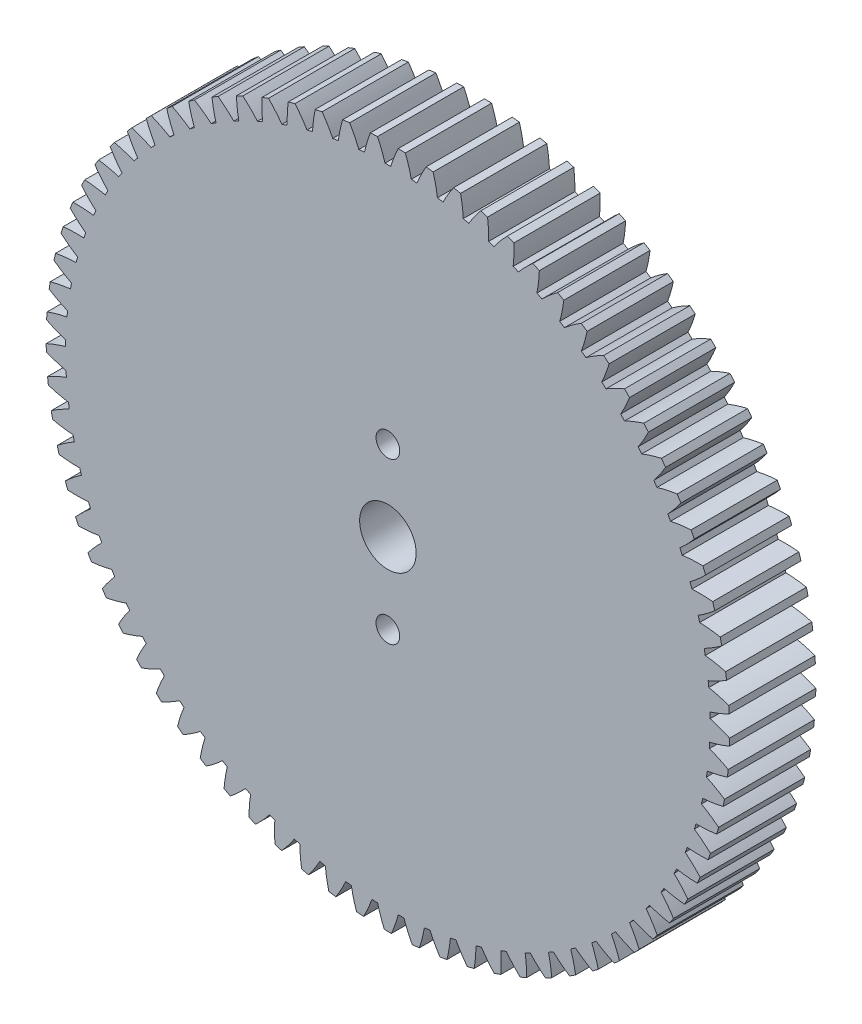
SolidWorks part; units mm, degrees
ref_plane "Front Plane" through (0, 0, 0) normal (0, 0, 1) x (1, 0, 0)
ref_plane "Top Plane" through (0, 0, 0) normal (0, 1, 0) x (1, 0, 0)
ref_plane "Right Plane" through (0, 0, 0) normal (1, 0, 0) x (0, 0, -1)
sketch "Model" plane through (0, 0, 0) normal (0, 0, 1) x (1, 0, 0)
  circle A3 centre (0, -9.3) radius 1.375
  circle A4 centre (0, 0) radius 3.275
  circle A5 centre (0, 9.3) radius 1.375
  arc A311 (-39.5739, 2.0126) -> (-37.3581, 1.0914) centre (-32.524, 15.8446) ccw
  arc A312 (-37.3581, 1.0914) -> (-37.3715, 0.4333) centre (0, 0) ccw
  arc A313 (-37.3715, 0.4333) -> (-39.623, -0.3968) centre (-33.1432, -14.5048) ccw
  arc A314 (-39.623, -0.3968) -> (-39.6062, -1.2197) centre (0, 0) ccw
  arc A315 (-39.6062, -1.2197) -> (-37.3227, -1.9572) centre (-33.7072, 13.1409) ccw
  arc A316 (-37.3227, -1.9572) -> (-37.2825, -2.6143) centre (0, 0) ccw
  arc A317 (-37.2825, -2.6143) -> (-39.4588, -3.6251) centre (-31.8506, -17.158) ccw
  arc A318 (-39.4588, -3.6251) -> (-39.375, -4.4439) centre (0, 0) ccw
  arc A319 (-39.375, -4.4439) -> (-37.039, -4.9929) centre (-34.6662, 10.3497) ccw
  arc A320 (-37.039, -4.9929) -> (-36.9453, -5.6445) centre (0, 0) ccw
  arc A321 (-36.9453, -5.6445) -> (-39.0321, -6.8293) centre (-30.3461, -19.6971) ccw
  arc A322 (-39.0321, -6.8293) -> (-38.8818, -7.6386) centre (0, 0) ccw
  arc A323 (-38.8818, -7.6386) -> (-36.5088, -7.9953) centre (-35.3944, 7.4897) ccw
  arc A324 (-36.5088, -7.9953) -> (-36.3623, -8.6371) centre (0, 0) ccw
  arc A325 (-36.3623, -8.6371) -> (-38.3455, -9.988) centre (-28.6396, -22.105) ccw
  arc A326 (-38.3455, -9.988) -> (-38.1298, -10.7824) centre (0, 0) ccw
  arc A327 (-38.1298, -10.7824) -> (-35.7356, -10.9445) centre (-35.8871, 4.5798) ccw
  arc A328 (-35.7356, -10.9445) -> (-35.5373, -11.5722) centre (0, 0) ccw
  arc A329 (-35.5373, -11.5722) -> (-37.4038, -13.0803) centre (-26.7426, -24.3659) ccw
  arc A330 (-37.4038, -13.0803) -> (-37.124, -13.8544) centre (0, 0) ccw
  arc A331 (-37.124, -13.8544) -> (-34.7246, -13.8209) centre (-36.141, 1.6394) ccw
  arc A332 (-34.7246, -13.8209) -> (-34.4758, -14.4303) centre (0, 0) ccw
  arc A333 (-34.4758, -14.4303) -> (-36.2132, -16.0856) centre (-24.6675, -26.4646) ccw
  arc A334 (-36.2132, -16.0856) -> (-35.8713, -16.8343) centre (0, 0) ccw
  arc A335 (-35.8713, -16.8343) -> (-33.4826, -16.6052) centre (-36.1544, -1.3119) ccw
  arc A336 (-33.4826, -16.6052) -> (-33.1849, -17.1924) centre (0, 0) ccw
  arc A337 (-33.1849, -17.1924) -> (-34.7816, -18.9838) centre (-22.4283, -28.3871) ccw
  arc A338 (-34.7816, -18.9838) -> (-34.3797, -19.7021) centre (0, 0) ccw
  arc A339 (-34.3797, -19.7021) -> (-32.0177, -19.2791) centre (-35.9271, -4.2544) ccw
  arc A340 (-32.0177, -19.2791) -> (-31.6731, -19.8401) centre (0, 0) ccw
  arc A341 (-31.6731, -19.8401) -> (-33.1185, -21.7556) centre (-20.0399, -30.1208) ccw
  arc A342 (-33.1185, -21.7556) -> (-32.6594, -22.4388) centre (0, 0) ccw
  arc A343 (-32.6594, -22.4388) -> (-30.3397, -21.8247) centre (-35.4608, -7.1687) ccw
  arc A344 (-30.3397, -21.8247) -> (-29.9506, -22.3557) centre (0, 0) ccw
  arc A345 (-29.9506, -22.3557) -> (-31.235, -24.3827) centre (-17.5181, -31.654) ccw
  arc A346 (-31.235, -24.3827) -> (-30.7218, -25.0262) centre (0, 0) ccw
  arc A347 (-30.7218, -25.0262) -> (-28.4598, -24.2251) centre (-34.7585, -10.0352) ccw
  arc A348 (-28.4598, -24.2251) -> (-28.0287, -24.7226) centre (0, 0) ccw
  arc A349 (-28.0287, -24.7226) -> (-29.1437, -26.8475) centre (-14.8797, -32.9766) ccw
  arc A350 (-29.1437, -26.8475) -> (-28.5797, -27.4471) centre (0, 0) ccw
  arc A351 (-28.5797, -27.4471) -> (-26.3906, -26.4642) centre (-33.8249, -12.835) ccw
  arc A352 (-26.3906, -26.4642) -> (-25.9204, -26.9249) centre (0, 0) ccw
  arc A353 (-25.9204, -26.9249) -> (-26.8584, -29.1336) centre (-12.1423, -34.0797) ccw
  arc A354 (-26.8584, -29.1336) -> (-26.2474, -29.6852) centre (0, 0) ccw
  arc A355 (-26.2474, -29.6852) -> (-24.1457, -28.5272) centre (-32.6662, -15.5493) ccw
  arc A356 (-24.1457, -28.5272) -> (-23.6395, -28.9481) centre (0, 0) ccw
  arc A357 (-23.6395, -28.9481) -> (-24.3943, -31.2259) centre (-9.3241, -34.956) ccw
  arc A358 (-24.3943, -31.2259) -> (-23.7405, -31.7259) centre (0, 0) ccw
  arc A359 (-23.7405, -31.7259) -> (-21.7401, -30.4004) centre (-31.2901, -18.1602) ccw
  arc A360 (-21.7401, -30.4004) -> (-21.2013, -30.7786) centre (0, 0) ccw
  arc A361 (-21.2013, -30.7786) -> (-21.768, -33.1104) centre (-6.4438, -35.5997) ccw
  arc A362 (-21.768, -33.1104) -> (-21.0755, -33.5554) centre (0, 0) ccw
  arc A363 (-21.0755, -33.5554) -> (-19.1898, -32.0713) centre (-29.7057, -20.6502) ccw
  arc A364 (-19.1898, -32.0713) -> (-18.622, -32.4043) centre (0, 0) ccw
  arc A365 (-18.622, -32.4043) -> (-18.9967, -34.7745) centre (-3.5207, -36.0065) ccw
  arc A366 (-18.9967, -34.7745) -> (-18.2703, -35.1616) centre (0, 0) ccw
  arc A367 (-18.2703, -35.1616) -> (-16.5119, -33.5287) centre (-27.9237, -23.0027) ccw
  arc A368 (-16.5119, -33.5287) -> (-15.9188, -33.8143) centre (0, 0) ccw
  arc A369 (-15.9188, -33.8143) -> (-16.0991, -36.2072) centre (-0.5741, -36.1736) ccw
  arc A370 (-16.0991, -36.2072) -> (-15.3435, -36.5338) centre (0, 0) ccw
  arc A371 (-15.3435, -36.5338) -> (-13.724, -34.763) centre (-25.9559, -25.2022) ccw
  arc A372 (-13.724, -34.763) -> (-13.1096, -34.9993) centre (0, 0) ccw
  arc A373 (-13.1096, -34.9993) -> (-13.0943, -37.3989) centre (2.3763, -36.1) ccw
  arc A374 (-13.0943, -37.3989) -> (-12.3146, -37.6629) centre (0, 0) ccw
  arc A375 (-12.3146, -37.6629) -> (-10.8449, -35.766) centre (-23.8153, -27.234) ccw
  arc A376 (-10.8449, -35.766) -> (-10.2133, -35.9514) centre (0, 0) ccw
  arc A377 (-10.2133, -35.9514) -> (-10.0024, -38.3418) centre (5.3109, -35.7862) ccw
  arc A378 (-10.0024, -38.3418) -> (-9.2038, -38.5413) centre (0, 0) ccw
  arc A379 (-9.2038, -38.5413) -> (-7.8935, -36.5309) centre (-21.5162, -29.0846) ccw
  arc A380 (-7.8935, -36.5309) -> (-7.2489, -36.6643) centre (0, 0) ccw
  arc A381 (-7.2489, -36.6643) -> (-6.8439, -39.0295) centre (8.2101, -35.2343) ccw
  arc A382 (-6.8439, -39.0295) -> (-6.0317, -39.1632) centre (0, 0) ccw
  arc A383 (-6.0317, -39.1632) -> (-4.8897, -37.0528) centre (-19.074, -30.7416) ccw
  arc A384 (-4.8897, -37.0528) -> (-4.2363, -37.1331) centre (0, 0) ccw
  arc A385 (-4.2363, -37.1331) -> (-3.6398, -39.4575) centre (11.0547, -34.4478) ccw
  arc A386 (-3.6398, -39.4575) -> (-2.8194, -39.5246) centre (0, 0) ccw
  arc A387 (-2.8194, -39.5246) -> (-1.8532, -37.328) centre (-16.5048, -32.194) ccw
  arc A388 (-1.8532, -37.328) -> (-1.1955, -37.3549) centre (0, 0) ccw
  arc A389 (-1.1955, -37.3549) -> (-0.4116, -39.6229) centre (13.8257, -33.4321) ccw
  arc A390 (-0.4116, -39.6229) -> (0.4116, -39.6229) centre (0, 0) ccw
  arc A391 (0.4116, -39.6229) -> (1.1955, -37.3549) centre (-13.8257, -33.4321) ccw
  arc A392 (1.1955, -37.3549) -> (1.8532, -37.328) centre (0, 0) ccw
  arc A393 (1.8532, -37.328) -> (2.8194, -39.5246) centre (16.5048, -32.194) ccw
  arc A394 (2.8194, -39.5246) -> (3.6398, -39.4575) centre (0, 0) ccw
  arc A395 (3.6398, -39.4575) -> (4.2363, -37.1331) centre (-11.0547, -34.4478) ccw
  arc A396 (4.2363, -37.1331) -> (4.8897, -37.0528) centre (0, 0) ccw
  arc A397 (4.8897, -37.0528) -> (6.0317, -39.1632) centre (19.074, -30.7416) ccw
  arc A398 (6.0317, -39.1632) -> (6.8439, -39.0295) centre (0, 0) ccw
  arc A399 (6.8439, -39.0295) -> (7.2489, -36.6643) centre (-8.2101, -35.2343) ccw
  arc A400 (7.2489, -36.6643) -> (7.8935, -36.5309) centre (0, 0) ccw
  arc A401 (7.8935, -36.5309) -> (9.2038, -38.5413) centre (21.5162, -29.0846) ccw
  arc A402 (9.2038, -38.5413) -> (10.0024, -38.3418) centre (0, 0) ccw
  arc A403 (10.0024, -38.3418) -> (10.2133, -35.9514) centre (-5.3109, -35.7862) ccw
  arc A404 (10.2133, -35.9514) -> (10.8449, -35.766) centre (0, 0) ccw
  arc A405 (10.8449, -35.766) -> (12.3146, -37.6629) centre (23.8153, -27.234) ccw
  arc A406 (12.3146, -37.6629) -> (13.0943, -37.3989) centre (0, 0) ccw
  arc A407 (13.0943, -37.3989) -> (13.1096, -34.9993) centre (-2.3763, -36.1) ccw
  arc A408 (13.1096, -34.9993) -> (13.724, -34.763) centre (0, 0) ccw
  arc A409 (13.724, -34.763) -> (15.3435, -36.5338) centre (25.9559, -25.2022) ccw
  arc A410 (15.3435, -36.5338) -> (16.0991, -36.2072) centre (0, 0) ccw
  arc A411 (16.0991, -36.2072) -> (15.9188, -33.8143) centre (0.5741, -36.1736) ccw
  arc A412 (15.9188, -33.8143) -> (16.5119, -33.5287) centre (0, 0) ccw
  arc A413 (16.5119, -33.5287) -> (18.2703, -35.1616) centre (27.9237, -23.0027) ccw
  arc A414 (18.2703, -35.1616) -> (18.9967, -34.7745) centre (0, 0) ccw
  arc A415 (18.9967, -34.7745) -> (18.622, -32.4043) centre (3.5207, -36.0065) ccw
  arc A416 (18.622, -32.4043) -> (19.1898, -32.0713) centre (0, 0) ccw
  arc A417 (19.1898, -32.0713) -> (21.0755, -33.5554) centre (29.7057, -20.6502) ccw
  arc A418 (21.0755, -33.5554) -> (21.768, -33.1104) centre (0, 0) ccw
  arc A419 (21.768, -33.1104) -> (21.2013, -30.7786) centre (6.4438, -35.5997) ccw
  arc A420 (21.2013, -30.7786) -> (21.7401, -30.4004) centre (0, 0) ccw
  arc A421 (21.7401, -30.4004) -> (23.7405, -31.7259) centre (31.2901, -18.1602) ccw
  arc A422 (23.7405, -31.7259) -> (24.3943, -31.2259) centre (0, 0) ccw
  arc A423 (24.3943, -31.2259) -> (23.6395, -28.9481) centre (9.3241, -34.956) ccw
  arc A424 (23.6395, -28.9481) -> (24.1457, -28.5272) centre (0, 0) ccw
  arc A425 (24.1457, -28.5272) -> (26.2474, -29.6852) centre (32.6662, -15.5493) ccw
  arc A426 (26.2474, -29.6852) -> (26.8584, -29.1336) centre (0, 0) ccw
  arc A427 (26.8584, -29.1336) -> (25.9204, -26.9249) centre (12.1423, -34.0797) ccw
  arc A428 (25.9204, -26.9249) -> (26.3906, -26.4642) centre (0, 0) ccw
  arc A429 (26.3906, -26.4642) -> (28.5797, -27.4471) centre (33.8249, -12.835) ccw
  arc A430 (28.5797, -27.4471) -> (29.1437, -26.8475) centre (0, 0) ccw
  arc A431 (29.1437, -26.8475) -> (28.0287, -24.7226) centre (14.8797, -32.9766) ccw
  arc A432 (28.0287, -24.7226) -> (28.4598, -24.2251) centre (0, 0) ccw
  arc A433 (28.4598, -24.2251) -> (30.7218, -25.0262) centre (34.7585, -10.0352) ccw
  arc A434 (30.7218, -25.0262) -> (31.235, -24.3827) centre (0, 0) ccw
  arc A435 (31.235, -24.3827) -> (29.9506, -22.3557) centre (17.5181, -31.654) ccw
  arc A436 (29.9506, -22.3557) -> (30.3397, -21.8247) centre (0, 0) ccw
  arc A437 (30.3397, -21.8247) -> (32.6594, -22.4388) centre (35.4608, -7.1687) ccw
  arc A438 (32.6594, -22.4388) -> (33.1185, -21.7556) centre (0, 0) ccw
  arc A439 (33.1185, -21.7556) -> (31.6731, -19.8401) centre (20.0399, -30.1208) ccw
  arc A440 (31.6731, -19.8401) -> (32.0177, -19.2791) centre (0, 0) ccw
  arc A441 (32.0177, -19.2791) -> (34.3797, -19.7021) centre (35.9271, -4.2544) ccw
  arc A442 (34.3797, -19.7021) -> (34.7816, -18.9838) centre (0, 0) ccw
  arc A443 (34.7816, -18.9838) -> (33.1849, -17.1924) centre (22.4283, -28.3871) ccw
  arc A444 (33.1849, -17.1924) -> (33.4826, -16.6052) centre (0, 0) ccw
  arc A445 (33.4826, -16.6052) -> (35.8713, -16.8343) centre (36.1544, -1.3119) ccw
  arc A446 (35.8713, -16.8343) -> (36.2132, -16.0856) centre (0, 0) ccw
  arc A447 (36.2132, -16.0856) -> (34.4758, -14.4303) centre (24.6675, -26.4646) ccw
  arc A448 (34.4758, -14.4303) -> (34.7246, -13.8209) centre (0, 0) ccw
  arc A449 (34.7246, -13.8209) -> (37.124, -13.8544) centre (36.141, 1.6394) ccw
  arc A450 (37.124, -13.8544) -> (37.4038, -13.0803) centre (0, 0) ccw
  arc A451 (37.4038, -13.0803) -> (35.5373, -11.5722) centre (26.7426, -24.3659) ccw
  arc A452 (35.5373, -11.5722) -> (35.7356, -10.9445) centre (0, 0) ccw
  arc A453 (35.7356, -10.9445) -> (38.1298, -10.7824) centre (35.8871, 4.5798) ccw
  arc A454 (38.1298, -10.7824) -> (38.3455, -9.988) centre (0, 0) ccw
  arc A455 (38.3455, -9.988) -> (36.3623, -8.6371) centre (28.6396, -22.105) ccw
  arc A456 (36.3623, -8.6371) -> (36.5088, -7.9953) centre (0, 0) ccw
  arc A457 (36.5088, -7.9953) -> (38.8818, -7.6386) centre (35.3944, 7.4897) ccw
  arc A458 (38.8818, -7.6386) -> (39.0321, -6.8293) centre (0, 0) ccw
  arc A459 (39.0321, -6.8293) -> (36.9453, -5.6445) centre (30.3461, -19.6971) ccw
  arc A460 (36.9453, -5.6445) -> (37.039, -4.9929) centre (0, 0) ccw
  arc A461 (37.039, -4.9929) -> (39.375, -4.4439) centre (34.6662, 10.3497) ccw
  arc A462 (39.375, -4.4439) -> (39.4588, -3.6251) centre (0, 0) ccw
  arc A463 (39.4588, -3.6251) -> (37.2825, -2.6143) centre (31.8506, -17.158) ccw
  arc A464 (37.2825, -2.6143) -> (37.3227, -1.9572) centre (0, 0) ccw
  arc A465 (37.3227, -1.9572) -> (39.6062, -1.2197) centre (33.7072, 13.1409) ccw
  arc A466 (39.6062, -1.2197) -> (39.623, -0.3968) centre (0, 0) ccw
  arc A467 (39.623, -0.3968) -> (37.3715, 0.4333) centre (33.1432, -14.5048) ccw
  arc A468 (37.3715, 0.4333) -> (37.3581, 1.0914) centre (0, 0) ccw
  arc A469 (37.3581, 1.0914) -> (39.5739, 2.0126) centre (32.524, 15.8446) ccw
  arc A470 (39.5739, 2.0126) -> (39.5235, 2.8342) centre (0, 0) ccw
  arc A471 (39.5235, 2.8342) -> (37.2118, 3.478) centre (34.2152, -11.7551) ccw
  arc A472 (37.2118, 3.478) -> (37.1448, 4.1328) centre (0, 0) ccw
  arc A473 (37.1448, 4.1328) -> (39.2781, 5.2315) centre (31.1243, 18.4429) ccw
  arc A474 (39.2781, 5.2315) -> (39.161, 6.0463) centre (0, 0) ccw
  arc A475 (39.161, 6.0463) -> (36.8045, 6.4995) centre (35.0595, -8.9271) ccw
  arc A476 (36.8045, 6.4995) -> (36.6843, 7.1467) centre (0, 0) ccw
  arc A477 (36.6843, 7.1467) -> (38.721, 8.4157) centre (29.5174, 20.9185) ccw
  arc A478 (38.721, 8.4157) -> (38.5379, 9.2182) centre (0, 0) ccw
  arc A479 (38.5379, 9.2182) -> (36.1523, 9.4778) centre (35.6705, -6.0397) ccw
  arc A480 (36.1523, 9.4778) -> (35.9797, 10.113) centre (0, 0) ccw
  arc A481 (35.9797, 10.113) -> (37.9062, 11.5438) centre (27.7142, 23.2548) ccw
  arc A482 (37.9062, 11.5438) -> (37.6583, 12.3287) centre (0, 0) ccw
  arc A483 (37.6583, 12.3287) -> (35.2595, 12.393) centre (36.0441, -3.1122) ccw
  arc A484 (35.2595, 12.393) -> (35.0357, 13.0121) centre (0, 0) ccw
  arc A485 (35.0357, 13.0121) -> (36.8392, 14.5951) centre (25.7265, 25.4364) ccw
  arc A486 (36.8392, 14.5951) -> (36.5281, 15.3572) centre (0, 0) ccw
  arc A487 (36.5281, 15.3572) -> (34.132, 15.2257) centre (36.1778, -0.1639) ccw
  arc A488 (34.132, 15.2257) -> (33.8585, 15.8245) centre (0, 0) ccw
  arc A489 (33.8585, 15.8245) -> (35.5269, 17.5493) centre (23.5676, 27.4487) ccw
  arc A490 (35.5269, 17.5493) -> (35.1548, 18.2834) centre (0, 0) ccw
  arc A491 (35.1548, 18.2834) -> (32.7774, 17.9571) centre (36.0708, 2.7855) ccw
  arc A492 (32.7774, 17.9571) -> (32.456, 18.5316) centre (0, 0) ccw
  arc A493 (32.456, 18.5316) -> (33.9783, 20.3866) centre (21.2518, 29.2783) ccw
  arc A494 (33.9783, 20.3866) -> (33.5475, 21.088) centre (0, 0) ccw
  arc A495 (33.5475, 21.088) -> (31.2047, 20.569) centre (35.7237, 5.7163) ccw
  arc A496 (31.2047, 20.569) -> (30.8375, 21.1154) centre (0, 0) ccw
  arc A497 (30.8375, 21.1154) -> (32.2035, 23.0884) centre (18.7946, 30.9131) ccw
  arc A498 (32.2035, 23.0884) -> (31.717, 23.7523) centre (0, 0) ccw
  arc A499 (31.717, 23.7523) -> (29.4243, 23.0441) centre (35.1389, 8.6091) ccw
  arc A500 (29.4243, 23.0441) -> (29.0138, 23.5587) centre (0, 0) ccw
  arc A501 (29.0138, 23.5587) -> (30.2145, 25.6364) centre (16.2124, 32.3422) ccw
  arc A502 (30.2145, 25.6364) -> (29.6754, 26.2585) centre (0, 0) ccw
  arc A503 (29.6754, 26.2585) -> (27.448, 25.3657) centre (34.3203, 11.4446) ccw
  arc A504 (27.448, 25.3657) -> (26.997, 25.8452) centre (0, 0) ccw
  arc A505 (26.997, 25.8452) -> (28.0243, 28.0139) centre (13.5223, 33.556) ccw
  arc A506 (28.0243, 28.0139) -> (27.4364, 28.5899) centre (0, 0) ccw
  arc A507 (27.4364, 28.5899) -> (25.2892, 27.5186) centre (33.2732, 14.2039) ccw
  arc A508 (25.2892, 27.5186) -> (24.8006, 27.9598) centre (0, 0) ccw
  arc A509 (24.8006, 27.9598) -> (25.6477, 30.2049) centre (10.7421, 34.5466) ccw
  arc A510 (25.6477, 30.2049) -> (25.0148, 30.7311) centre (0, 0) ccw
  arc A511 (25.0148, 30.7311) -> (22.962, 29.4883) centre (32.0048, 16.8688) ccw
  arc A512 (22.962, 29.4883) -> (22.4391, 29.8882) centre (0, 0) ccw
  arc A513 (22.4391, 29.8882) -> (23.1004, 32.1949) centre (7.8905, 35.3072) ccw
  arc A514 (23.1004, 32.1949) -> (22.4266, 32.6678) centre (0, 0) ccw
  arc A515 (22.4266, 32.6678) -> (20.482, 31.2618) centre (30.5233, 19.4213) ccw
  arc A516 (20.482, 31.2618) -> (19.9282, 31.6177) centre (0, 0) ccw
  arc A517 (19.9282, 31.6177) -> (20.3993, 33.9707) centre (4.9864, 35.8329) ccw
  arc A518 (20.3993, 33.9707) -> (19.6893, 34.3871) centre (0, 0) ccw
  arc A519 (19.6893, 34.3871) -> (17.8657, 32.8273) centre (28.8387, 21.8446) ccw
  arc A520 (17.8657, 32.8273) -> (17.2848, 33.1369) centre (0, 0) ccw
  arc A521 (17.2848, 33.1369) -> (17.5625, 35.5204) centre (2.0491, 36.1201) ccw
  arc A522 (17.5625, 35.5204) -> (16.8209, 35.8775) centre (0, 0) ccw
  arc A523 (16.8209, 35.8775) -> (15.1306, 34.1743) centre (26.9622, 24.1226) ccw
  arc A524 (15.1306, 34.1743) -> (14.5263, 34.4355) centre (0, 0) ccw
  arc A525 (14.5263, 34.4355) -> (14.6088, 36.8337) centre (-0.9018, 36.1669) ccw
  arc A526 (14.6088, 36.8337) -> (13.8406, 37.1292) centre (0, 0) ccw
  arc A527 (13.8406, 37.1292) -> (12.2947, 35.2939) centre (24.9063, 26.24) ccw
  arc A528 (12.2947, 35.2939) -> (11.6712, 35.5049) centre (0, 0) ccw
  arc A529 (11.6712, 35.5049) -> (11.5579, 37.9019) centre (-3.8468, 35.9731) ccw
  arc A530 (11.5579, 37.9019) -> (10.7682, 38.1338) centre (0, 0) ccw
  arc A531 (10.7682, 38.1338) -> (9.377, 36.1786) centre (22.6846, 28.1828) ccw
  arc A532 (9.377, 36.1786) -> (8.7384, 36.3381) centre (0, 0) ccw
  arc A533 (8.7384, 36.3381) -> (8.4301, 38.7179) centre (-6.7661, 35.5398) ccw
  arc A534 (8.4301, 38.7179) -> (7.6241, 38.8846) centre (0, 0) ccw
  arc A535 (7.6241, 38.8846) -> (6.3969, 36.8225) centre (20.312, 29.938) ccw
  arc A536 (6.3969, 36.8225) -> (5.7474, 36.9294) centre (0, 0) ccw
  arc A537 (5.7474, 36.9294) -> (5.2462, 39.2762) centre (-9.6404, 34.8701) ccw
  arc A538 (5.2462, 39.2762) -> (4.4292, 39.3767) centre (0, 0) ccw
  arc A539 (4.4292, 39.3767) -> (3.3743, 37.2214) centre (17.8042, 31.494) ccw
  arc A540 (3.3743, 37.2214) -> (2.7182, 37.275) centre (0, 0) ccw
  arc A541 (2.7182, 37.275) -> (2.0274, 39.5731) centre (-12.4506, 33.9683) ccw
  arc A542 (2.0274, 39.5731) -> (1.2049, 39.6067) centre (0, 0) ccw
  arc A543 (1.2049, 39.6067) -> (0.3291, 37.3726) centre (15.1779, 32.8404) ccw
  arc A544 (0.3291, 37.3726) -> (-0.3291, 37.3726) centre (0, 0) ccw
  arc A545 (-0.3291, 37.3726) -> (-1.2049, 39.6067) centre (-15.1779, 32.8404) ccw
  arc A546 (-1.2049, 39.6067) -> (-2.0274, 39.5731) centre (0, 0) ccw
  arc A547 (-2.0274, 39.5731) -> (-2.7182, 37.275) centre (12.4506, 33.9683) ccw
  arc A548 (-2.7182, 37.275) -> (-3.3743, 37.2214) centre (0, 0) ccw
  arc A549 (-3.3743, 37.2214) -> (-4.4292, 39.3767) centre (-17.8042, 31.494) ccw
  arc A550 (-4.4292, 39.3767) -> (-5.2462, 39.2762) centre (0, 0) ccw
  arc A551 (-5.2462, 39.2762) -> (-5.7474, 36.9294) centre (9.6404, 34.8701) ccw
  arc A552 (-5.7474, 36.9294) -> (-6.3969, 36.8225) centre (0, 0) ccw
  arc A553 (-6.3969, 36.8225) -> (-7.6241, 38.8846) centre (-20.312, 29.938) ccw
  arc A554 (-7.6241, 38.8846) -> (-8.4301, 38.7179) centre (0, 0) ccw
  arc A555 (-8.4301, 38.7179) -> (-8.7384, 36.3381) centre (6.7661, 35.5398) ccw
  arc A556 (-8.7384, 36.3381) -> (-9.377, 36.1786) centre (0, 0) ccw
  arc A557 (-9.377, 36.1786) -> (-10.7682, 38.1338) centre (-22.6846, 28.1828) ccw
  arc A558 (-10.7682, 38.1338) -> (-11.5579, 37.9019) centre (0, 0) ccw
  arc A559 (-11.5579, 37.9019) -> (-11.6712, 35.5049) centre (3.8468, 35.9731) ccw
  arc A560 (-11.6712, 35.5049) -> (-12.2947, 35.2939) centre (0, 0) ccw
  arc A561 (-12.2947, 35.2939) -> (-13.8406, 37.1292) centre (-24.9063, 26.24) ccw
  arc A562 (-13.8406, 37.1292) -> (-14.6088, 36.8337) centre (0, 0) ccw
  arc A563 (-14.6088, 36.8337) -> (-14.5263, 34.4355) centre (0.9018, 36.1669) ccw
  arc A564 (-14.5263, 34.4355) -> (-15.1306, 34.1743) centre (0, 0) ccw
  arc A565 (-15.1306, 34.1743) -> (-16.8209, 35.8775) centre (-26.9622, 24.1226) ccw
  arc A566 (-16.8209, 35.8775) -> (-17.5625, 35.5204) centre (0, 0) ccw
  arc A567 (-17.5625, 35.5204) -> (-17.2848, 33.1369) centre (-2.0491, 36.1201) ccw
  arc A568 (-17.2848, 33.1369) -> (-17.8657, 32.8273) centre (0, 0) ccw
  arc A569 (-17.8657, 32.8273) -> (-19.6893, 34.3871) centre (-28.8387, 21.8446) ccw
  arc A570 (-19.6893, 34.3871) -> (-20.3993, 33.9707) centre (0, 0) ccw
  arc A571 (-20.3993, 33.9707) -> (-19.9282, 31.6177) centre (-4.9864, 35.8329) ccw
  arc A572 (-19.9282, 31.6177) -> (-20.482, 31.2618) centre (0, 0) ccw
  arc A573 (-20.482, 31.2618) -> (-22.4266, 32.6678) centre (-30.5233, 19.4213) ccw
  arc A574 (-22.4266, 32.6678) -> (-23.1004, 32.1949) centre (0, 0) ccw
  arc A575 (-23.1004, 32.1949) -> (-22.4391, 29.8882) centre (-7.8905, 35.3072) ccw
  arc A576 (-22.4391, 29.8882) -> (-22.962, 29.4883) centre (0, 0) ccw
  arc A577 (-22.962, 29.4883) -> (-25.0148, 30.7311) centre (-32.0048, 16.8688) ccw
  arc A578 (-25.0148, 30.7311) -> (-25.6477, 30.2049) centre (0, 0) ccw
  arc A579 (-25.6477, 30.2049) -> (-24.8006, 27.9598) centre (-10.7421, 34.5466) ccw
  arc A580 (-24.8006, 27.9598) -> (-25.2892, 27.5186) centre (0, 0) ccw
  arc A581 (-25.2892, 27.5186) -> (-27.4364, 28.5899) centre (-33.2732, 14.2039) ccw
  arc A582 (-27.4364, 28.5899) -> (-28.0243, 28.0139) centre (0, 0) ccw
  arc A583 (-28.0243, 28.0139) -> (-26.997, 25.8452) centre (-13.5223, 33.556) ccw
  arc A584 (-26.997, 25.8452) -> (-27.448, 25.3657) centre (0, 0) ccw
  arc A585 (-27.448, 25.3657) -> (-29.6754, 26.2585) centre (-34.3203, 11.4446) ccw
  arc A586 (-29.6754, 26.2585) -> (-30.2145, 25.6364) centre (0, 0) ccw
  arc A587 (-30.2145, 25.6364) -> (-29.0138, 23.5587) centre (-16.2124, 32.3422) ccw
  arc A588 (-29.0138, 23.5587) -> (-29.4243, 23.0441) centre (0, 0) ccw
  arc A589 (-29.4243, 23.0441) -> (-31.717, 23.7523) centre (-35.1389, 8.6091) ccw
  arc A590 (-31.717, 23.7523) -> (-32.2035, 23.0884) centre (0, 0) ccw
  arc A591 (-32.2035, 23.0884) -> (-30.8375, 21.1154) centre (-18.7946, 30.9131) ccw
  arc A592 (-30.8375, 21.1154) -> (-31.2047, 20.569) centre (0, 0) ccw
  arc A593 (-31.2047, 20.569) -> (-33.5475, 21.088) centre (-35.7237, 5.7163) ccw
  arc A594 (-33.5475, 21.088) -> (-33.9783, 20.3866) centre (0, 0) ccw
  arc A595 (-33.9783, 20.3866) -> (-32.456, 18.5316) centre (-21.2518, 29.2783) ccw
  arc A596 (-32.456, 18.5316) -> (-32.7774, 17.9571) centre (0, 0) ccw
  arc A597 (-32.7774, 17.9571) -> (-35.1548, 18.2834) centre (-36.0708, 2.7855) ccw
  arc A598 (-35.1548, 18.2834) -> (-35.5269, 17.5493) centre (0, 0) ccw
  arc A599 (-35.5269, 17.5493) -> (-33.8585, 15.8245) centre (-23.5676, 27.4487) ccw
  arc A600 (-33.8585, 15.8245) -> (-34.132, 15.2257) centre (0, 0) ccw
  arc A601 (-34.132, 15.2257) -> (-36.5281, 15.3572) centre (-36.1778, -0.1639) ccw
  arc A602 (-36.5281, 15.3572) -> (-36.8392, 14.5951) centre (0, 0) ccw
  arc A603 (-36.8392, 14.5951) -> (-35.0357, 13.0121) centre (-25.7265, 25.4364) ccw
  arc A604 (-35.0357, 13.0121) -> (-35.2595, 12.393) centre (0, 0) ccw
  arc A605 (-35.2595, 12.393) -> (-37.6583, 12.3287) centre (-36.0441, -3.1122) ccw
  arc A606 (-37.6583, 12.3287) -> (-37.9062, 11.5438) centre (0, 0) ccw
  arc A607 (-37.9062, 11.5438) -> (-35.9797, 10.113) centre (-27.7142, 23.2548) ccw
  arc A608 (-35.9797, 10.113) -> (-36.1523, 9.4778) centre (0, 0) ccw
  arc A609 (-36.1523, 9.4778) -> (-38.5379, 9.2182) centre (-35.6705, -6.0397) ccw
  arc A610 (-38.5379, 9.2182) -> (-38.721, 8.4157) centre (0, 0) ccw
  arc A611 (-38.721, 8.4157) -> (-36.6843, 7.1467) centre (-29.5174, 20.9185) ccw
  arc A612 (-36.6843, 7.1467) -> (-36.8045, 6.4995) centre (0, 0) ccw
  arc A613 (-36.8045, 6.4995) -> (-39.161, 6.0463) centre (-35.0595, -8.9271) ccw
  arc A614 (-39.161, 6.0463) -> (-39.2781, 5.2315) centre (0, 0) ccw
  arc A615 (-39.2781, 5.2315) -> (-37.1448, 4.1328) centre (-31.1243, 18.4429) ccw
  arc A616 (-37.1448, 4.1328) -> (-37.2118, 3.478) centre (0, 0) ccw
  arc A617 (-37.2118, 3.478) -> (-39.5235, 2.8342) centre (-34.2152, -11.7551) ccw
  arc A618 (-39.5235, 2.8342) -> (-39.5739, 2.0126) centre (0, 0) ccw
extrude "Boss-Extrude1" add sketch "Model" along normal blind 10
